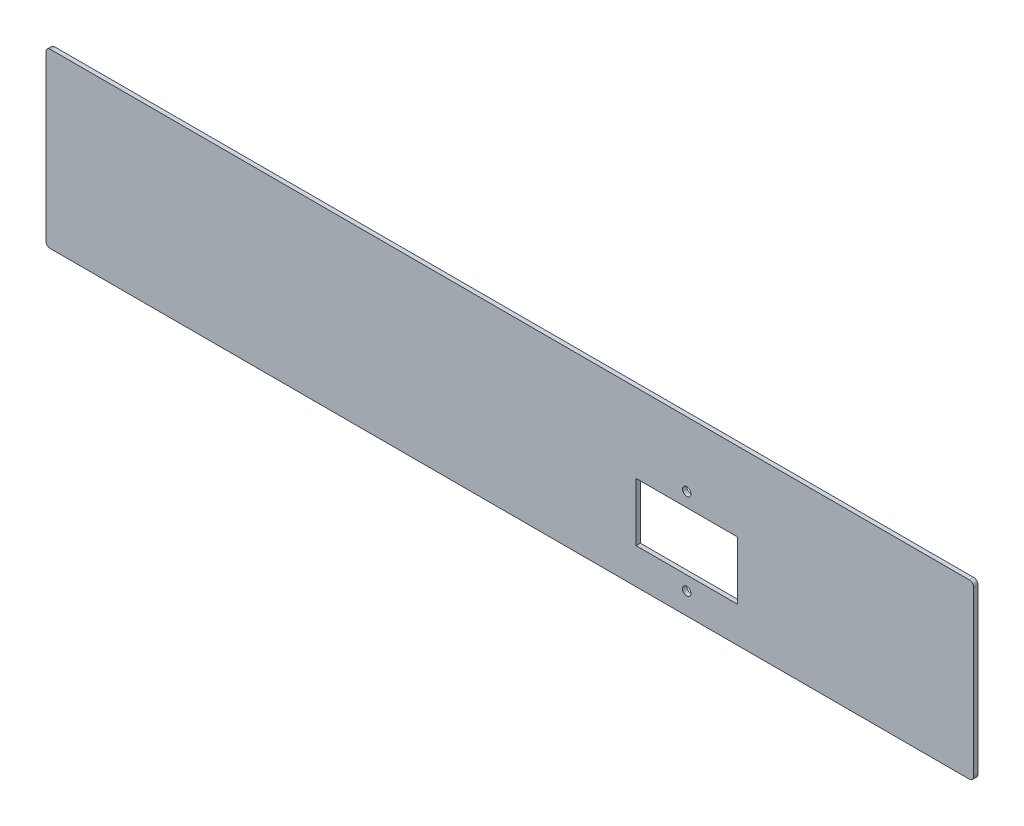
SolidWorks part; units mm, degrees
ref_plane "Front Plane" through (0, 0, 0) normal (0, 0, 1) x (1, 0, 0)
ref_plane "Top Plane" through (0, 0, 0) normal (0, 1, 0) x (1, 0, 0)
ref_plane "Right Plane" through (0, 0, 0) normal (1, 0, 0) x (0, 0, -1)
sketch "Sketch1" plane through (0, 0, 0) normal (0, 0, 1) x (1, 0, 0)
  line L1 (-352.9248, 45.7035) -> (77.0752, 45.7035)
  line L2 (-352.9248, 45.7035) -> (-352.9248, -34.2965)
  line L3 (-352.9248, -34.2965) -> (77.0752, -34.2965)
  line L4 (77.0752, 45.7035) -> (77.0752, -34.2965)
  line L5 (-79.4248, 9.2035) -> (-32.4248, 9.2035)
  line L6 (-79.4248, 9.2035) -> (-79.4248, -17.7965)
  line L7 (-79.4248, -17.7965) -> (-32.4248, -17.7965)
  line L8 (-32.4248, 9.2035) -> (-32.4248, -17.7965)
  circle A0 centre (-55.9248, 15.7035) radius 1.95
  circle A1 centre (-55.9248, -24.2965) radius 1.95
  point P12 (-55.9248, 9.2035)
  dimension "D3" = 133
  dimension "D4" = 40
  dimension "D1" = 430
  dimension "D2" = 80
  dimension "D5" = 10
  dimension "D6" = 47
  dimension "D7" = 27
  dimension "D8" = 6.5
extrude "Boss-Extrude1" add sketch "Sketch1" along normal blind 2
fillet "Fillet1" radius 2 4 edges at (77.0752, 45.7035, 1) (77.0752, -34.2965, 1) (-352.9248, -34.2965, 1) (-352.9248, 45.7035, 1)
